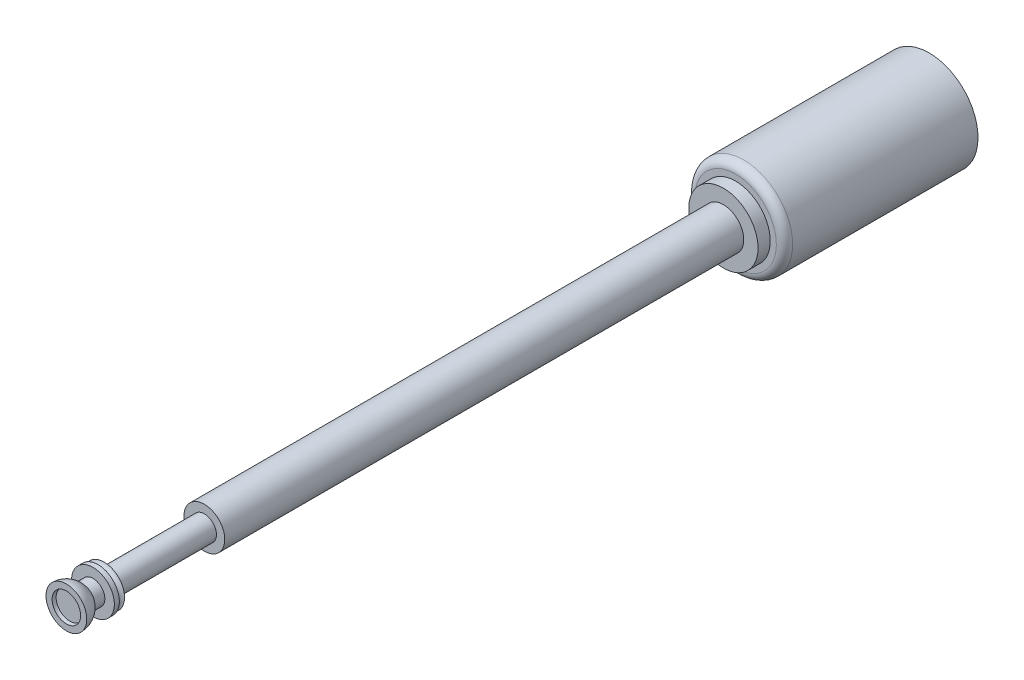
SolidWorks part; units mm, degrees
ref_plane "Front Plane" through (0, 0, 0) normal (0, 0, 1) x (1, 0, 0)
ref_plane "Top Plane" through (0, 0, 0) normal (0, 1, 0) x (1, 0, 0)
ref_plane "Right Plane" through (0, 0, 0) normal (1, 0, 0) x (0, 0, -1)
sketch "Sketch2" plane through (0, 0, 0) normal (0, 0, 1) x (1, 0, 0)
  circle A0 centre (0, 0) radius 0.5
  circle A1 centre (0, 0) radius 1.2
  dimension "D1" = 2.4
  dimension "D2" = 1
extrude "Boss-Extrude1" add sketch "Sketch2" along normal blind 15.5 contours A0
extrude "Boss-Extrude3" add sketch "Sketch2<6>" along direction (0, 0, 1) on the side against the normal blind 4.75 separate body
sketch "Sketch2<6>" plane through (0, 0, 0) normal (0, 0, 1) x (1, 0, 0) same geometry as "Sketch2"
sketch "Sketch3" plane through (0, 0, 0) normal (0, 0, -1) x (-1, 0, 0)
  circle A1 centre (0, 0) radius 0.5
  circle A2 centre (0, 0) radius 0.5
  dimension "D1" = 0
extrude "Boss-Extrude4" add sketch "Sketch3" along normal blind 4.75
fillet "Fillet1" radius 0.2 1 edges at (1.2, 0, 0)
sketch "Sketch4" plane through (0, 0, 0) normal (0, 0, 1) x (1, 0, 0)
  circle A0 centre (0, 0) radius 0.85
  dimension "D1" = 1.7
extrude "Boss-Extrude5" add sketch "Sketch4" along normal blind 0.3
sketch "Sketch5" plane through (0, 0, 0) normal (0, 1, 0) x (1, 0, 0)
  line L0 (0.5, -15.5) -> (0, -15.5)
  line L1 (-0.5, -15.5) -> (0.5, -15.5) construction
  line L2 (0, -15.5) -> (0, -16.0775)
  line L3 (0.35, -16.4275) -> (0.5, -16.4275)
  line L4 (0.2917, -16.0214) -> (0.2917, -15.7742)
  line L5 (0.2917, -15.7742) -> (0.5249, -15.7742)
  line L6 (0.5249, -15.7742) -> (0.5249, -15.6524)
  line L7 (0.5249, -15.6524) -> (0.3768, -15.6524)
  arc A0 (0, -16.0775) -> (0.35, -16.4275) centre (0, -16.4275) cw
  arc A1 (0.5, -16.4275) -> (0.2917, -16.0214) centre (0, -16.4275) ccw
  arc A2 (0.3768, -15.6524) -> (0.5, -15.5) centre (0.5326, -15.6524) cw
  dimension "D1" = 0.9275
  dimension "D2" = 0.35
  dimension "D3" = 0.5
revolve "Revolve1" add sketch "Sketch5" angle 360 about L2
sketch "Sketch6" plane through (0, 0, 0) normal (0, 1, 0) x (1, 0, 0)
  line L0 (0, -16.4275) -> (0, -15.5) construction
  line L1 (-0.5, -16.4275) -> (0.5, -16.4275) construction
  line L2 (0.5, -15.5) -> (-0.5, -15.5) construction
  line L4 (0, -16.3087) -> (-0.4667, -16.3087)
  line L5 (0, -16.3087) -> (0, -16.34)
  line L6 (0, -16.34) -> (-0.4667, -16.34)
  line L7 (-0.4667, -16.3087) -> (-0.4667, -16.34)
  dimension "D1" = 0.84
revolve "Revolve2" add sketch "Sketch6" angle 360 about L0
sketch "Sketch7" plane through (0, 0, 0) normal (0, 1, 0) x (1, 0, 0)
  line L0 (0.5, -15.5) -> (-0.5, -15.5) construction
  line L1 (-0.2962, -15.5) -> (-1.8061, -15.5)
  line L2 (-0.2962, -15.5) -> (-0.2962, -13.04)
  line L3 (-0.2962, -13.04) -> (-1.8061, -13.04)
  line L4 (-1.8061, -15.5) -> (-1.8061, -13.04)
  line L5 (0, -15.5) -> (0, -16.6112) construction
  dimension "D1" = 2.46
  dimension "D2" = 0.2962
revolve "Cut-Revolve1" cut sketch "Sketch7" angle 360 about L5
sketch "Sketch8" plane through (0, 0, -4.75) normal (0, 0, -1) x (-1, 0, 0)
  point P0 (0, 0)
